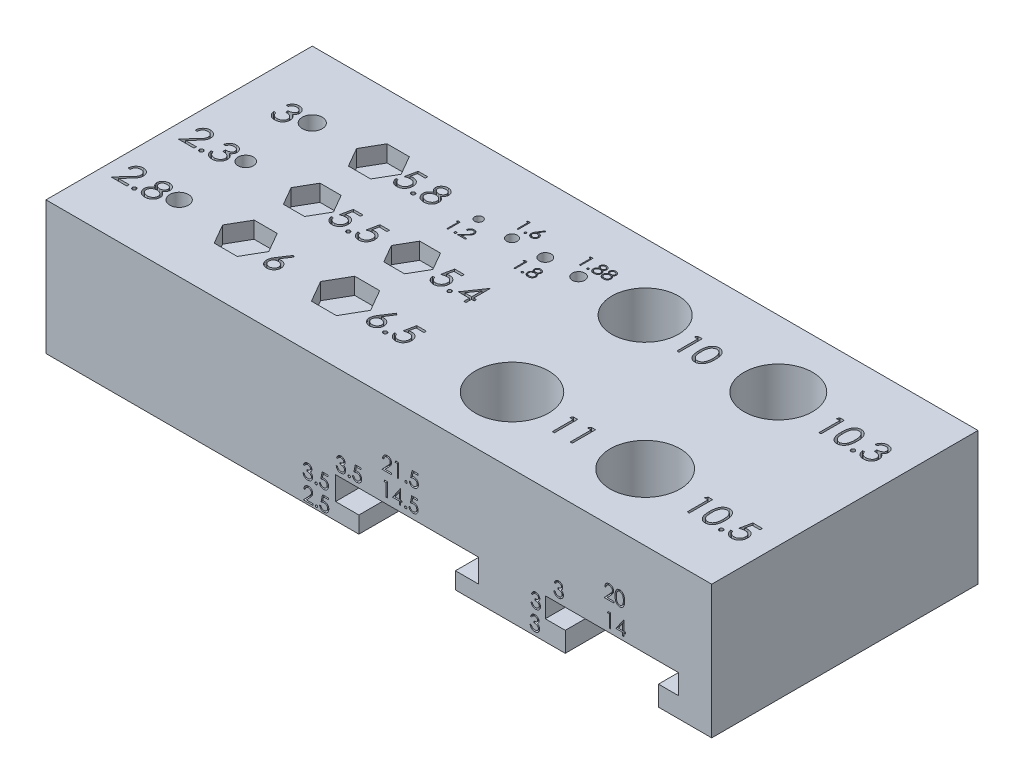
SolidWorks part; units mm, degrees
ref_plane "Front Plane" through (0, 0, 0) normal (0, 0, 1) x (1, 0, 0)
ref_plane "Top Plane" through (0, 0, 0) normal (0, 1, 0) x (1, 0, 0)
ref_plane "Right Plane" through (0, 0, 0) normal (1, 0, 0) x (0, 0, -1)
sketch "Sketch1" plane through (0, 0, 0) normal (0, 1, 0) x (1, 0, 0)
  line L1 (-50, 20) -> (50, 20)
  line L2 (-50, 20) -> (-50, -20)
  line L3 (-50, -20) -> (50, -20)
  line L4 (50, 20) -> (50, -20)
  line L5 (-50, 20) -> (50, -20) construction
  line L6 (-50, -20) -> (50, 20) construction
  point P0 (0, 0)
  dimension "D1" = 100
  dimension "D2" = 40
extrude "Boss-Extrude1" add sketch "Sketch1" along normal blind 15 and the other way blind 5
sketch "Sketch2" plane through (0, 15, 0) normal (0, 1, 0) x (1, 0, 0)
  line L0 (-55.0226, 0) -> (74.4605, 0) construction
  line L1 (0, -20.9292) -> (0, 35.5333) construction
  line L2 (-15, 35.5333) -> (-15, -25.6601) construction
  line L3 (-30, 35.5333) -> (-30, -25.6601) construction
  line L4 (-45, 35.5333) -> (-45, -26.8859) construction
  line L5 (-55.0226, 10) -> (73.221, 10) construction
  line L6 (-26.8246, 0) -> (-28.4123, 2.75)
  line L7 (-28.4123, 2.75) -> (-31.5877, 2.75)
  line L8 (-31.5877, 2.75) -> (-33.1754, 0)
  line L9 (-33.1754, 0) -> (-31.5877, -2.75)
  line L10 (-31.5877, -2.75) -> (-28.4123, -2.75)
  line L11 (-28.4123, -2.75) -> (-26.8246, 0)
  line L12 (-55.0226, -10) -> (70.5333, -10) construction
  line L14 (-26.6514, 10) -> (-28.3257, 12.9)
  line L15 (-28.3257, 12.9) -> (-31.6743, 12.9)
  line L16 (-31.6743, 12.9) -> (-33.3486, 10)
  line L17 (-33.3486, 10) -> (-31.6743, 7.1)
  line L18 (-31.6743, 7.1) -> (-28.3257, 7.1)
  line L19 (-28.3257, 7.1) -> (-26.6514, 10)
  line L20 (-26.5359, -10) -> (-28.2679, -7)
  line L21 (-28.2679, -7) -> (-31.7321, -7)
  line L22 (-31.7321, -7) -> (-33.4641, -10)
  line L23 (-33.4641, -10) -> (-31.7321, -13)
  line L24 (-31.7321, -13) -> (-28.2679, -13)
  line L25 (-28.2679, -13) -> (-26.5359, -10)
  line L26 (-11.2472, -10) -> (-13.1236, -6.75)
  line L27 (-13.1236, -6.75) -> (-16.8764, -6.75)
  line L28 (-16.8764, -6.75) -> (-18.7528, -10)
  line L29 (-18.7528, -10) -> (-16.8764, -13.25)
  line L30 (-16.8764, -13.25) -> (-13.1236, -13.25)
  line L31 (-13.1236, -13.25) -> (-11.2472, -10)
  line L32 (-11.8823, 0) -> (-13.4412, 2.7)
  line L33 (-13.4412, 2.7) -> (-16.5588, 2.7)
  line L34 (-16.5588, 2.7) -> (-18.1177, 0)
  line L35 (-18.1177, 0) -> (-16.5588, -2.7)
  line L36 (-16.5588, -2.7) -> (-13.4412, -2.7)
  line L37 (-13.4412, -2.7) -> (-11.8823, 0)
  circle A0 centre (-30, 0) radius 2.75 construction
  circle A1 centre (-30, 10) radius 2.9 construction
  circle A2 centre (-30, -10) radius 3 construction
  circle A3 centre (-15, -10) radius 3.25 construction
  circle A4 centre (-15, 0) radius 2.7 construction
  point P11 (-30, 0)
  point P24 (-30, 10)
  point P25 (-30, -10)
  point P35 (-15, -10)
  point P43 (-15, 0)
  point P44 (-15, 10)
  point P54 (-32.5981, -11.5)
  point P62 (-27.4019, -8.5)
  point P63 (-32.3816, -1.375)
  point P64 (-45, 10)
  point P65 (-45, 0)
  point P66 (-45, -10)
  dimension "D1" = 15
  dimension "D2" = 15
  dimension "D3" = 15
  dimension "D4" = 6
  dimension "D5" = 10
  dimension "D6" = 10
  dimension "D7" = 5.5
  dimension "D8" = 5.8
  dimension "D9" = 6.5
  dimension "D10" = 5.4
extrude "Cut-Extrude2" cut sketch "Sketch2" against normal blind 2.5
sketch "Sketch4" plane through (0, 15, 0) normal (0, 1, 0) x (1, 0, 0)
  line L0 (-51.3652, 0) -> (12.805, 0) construction
  line L1 (-33.3486, 10) -> (13.2716, 10) construction
  line L2 (-33.4641, -10) -> (12.805, -10) construction
  line L3 (-26.6514, 15.317) -> (-26.6514, -17.9931) construction
  text T0 "5.5\r\n"
  text T1 "5.8\r\n"
  text T2 "6\r\n"
  text T3 "6.5"
  text T4 "5.4"
  point P9 (-26.8246, 0)
  point P10 (-11.8823, 0)
  point P12 (-26.6514, 10)
  point P14 (-26.5359, -10)
  point P16 (-11.2472, -10)
extrude "Cut-Extrude3" cut sketch "Sketch4" against normal blind 1
sketch "Sketch5" plane through (0, 15, 0) normal (0, 1, 0) x (1, 0, 0)
  line L0 (-53.0216, 0) -> (7.0622, 0) construction
  line L1 (-40, 20.4528) -> (-40, -20.8884) construction
  line L2 (-50, 20) -> (-50, -20) construction
  line L3 (-53.3145, 10) -> (-2.602, 10) construction
  line L4 (-53.3145, -10) -> (1.0099, -10) construction
  circle A0 centre (-40, 0) radius 1.15
  circle A1 centre (-40, 10) radius 1.5
  circle A2 centre (-40, -10) radius 1.4
  point P11 (-40, 10)
  point P12 (-40, 0)
  point P13 (-40, -10)
  dimension "D4" = 3
  dimension "D5" = 2.3
  dimension "D6" = 2.8
  dimension "D1" = 10
  dimension "D2" = 10
  dimension "D3" = 10
extrude "Cut-Extrude4" cut sketch "Sketch5" against normal through all
sketch "Sketch6" plane through (0, 15, 0) normal (0, 1, 0) x (1, 0, 0)
  text T0 "3"
  text T1 "2.3\r\n"
  text T2 "2.8\r\n"
extrude "Cut-Extrude5" cut sketch "Sketch6" against normal blind 1
sketch "Sketch7" plane through (0, 15, 0) normal (0, 1, 0) x (1, 0, 0)
  line L0 (-58.108, 0) -> (70.6552, 0) construction
  line L1 (10, 29.8768) -> (10, -34.402) construction
  line L2 (30, 29.8768) -> (30, -36.2532) construction
  line L3 (50, -20) -> (50, 20) construction
  line L4 (63.2503, 10) -> (-10.3874, 10) construction
  line L5 (0, -10) -> (69.4211, -10) construction
  circle A0 centre (10, 10) radius 5
  circle A1 centre (30, 10) radius 5.15
  circle A2 centre (30, -10) radius 5.25
  circle A3 centre (10, -10) radius 5.5
  point P13 (10, 10)
  point P14 (30, 10)
  point P15 (30, -10)
  point P16 (10, -10)
  dimension "D5" = 10
  dimension "D6" = 11
  dimension "D7" = 10.5
  dimension "D8" = 10.3
  dimension "D1" = 20
  dimension "D2" = 20
  dimension "D3" = 10
  dimension "D4" = 10
extrude "Cut-Extrude6" cut sketch "Sketch7" against normal blind 10
sketch "Sketch8" plane through (0, 15, 0) normal (0, 1, 0) x (1, 0, 0)
  text T0 "10\r\n"
  text T1 "11"
  text T2 "10.3\r\n"
  text T3 "10.5"
extrude "Cut-Extrude7" cut sketch "Sketch8" against normal blind 1
sketch "Sketch9" plane through (0, 0, 20) normal (0, 0, 1) x (1, 0, 0)
  line L0 (53.7715, 1) -> (-9.5236, 1) construction
  line L1 (45, 17.6721) -> (45, -16.7465) construction
  line L2 (25, 18.1388) -> (25, -16.7465) construction
  line L3 (53.7715, -2) -> (-2.4066, -2) construction
  line L4 (-50, -5) -> (50, -5) construction
  line L5 (50, -5) -> (50, 15) construction
  line L6 (28, -9.1919) -> (28, 15.8625) construction
  line L7 (42, 15.8625) -> (42, -9.1919) construction
  line L8 (-3, -5) -> (-3, -2.5)
  line L9 (28, -5) -> (28, -2)
  line L10 (28, -2) -> (25, -2)
  line L11 (25, -2) -> (25, 1)
  line L12 (25, 1) -> (45, 1)
  line L13 (45, 1) -> (45, -2)
  line L14 (45, -2) -> (42, -2)
  line L15 (42, -2) -> (42, -5)
  line L16 (42, -5) -> (28, -5)
  line L17 (15, -5) -> (15, 11.272) construction
  line L18 (-6.5, -5) -> (-6.5, 13.9547) construction
  line L19 (-3, 16.4059) -> (-3, -11.3441) construction
  line L20 (11.5, 16.8381) -> (11.5, -11.3441) construction
  line L21 (-10.0811, -2.5) -> (47.089, -2.5) construction
  line L22 (-3, -2.5) -> (-6.5, -2.5)
  line L23 (-6.5, -2.5) -> (-6.5, 1)
  line L24 (-6.5, 1) -> (15, 1)
  line L25 (15, 1) -> (15, -2.5)
  line L26 (15, -2.5) -> (11.5, -2.5)
  line L27 (11.5, -2.5) -> (11.5, -5)
  line L28 (11.5, -5) -> (-3, -5)
  point P33 (15, 3.136)
  dimension "D1" = 3
  dimension "D2" = 3
  dimension "D3" = 5
  dimension "D4" = 20
  dimension "D5" = 3
  dimension "D6" = 3
  dimension "D7" = 3.5
  dimension "D8" = 21.5
  dimension "D9" = 2.5
  dimension "D10" = 3.5
  dimension "D11" = 10
extrude "Cut-Extrude9" cut sketch "Sketch9" against normal through all
sketch "Sketch10" plane through (0, 0, 20) normal (0, 0, 1) x (1, 0, 0)
  text T0 "21.5" font "Century Gothic" height in points 8
  text T1 "2.5\r\n" font "Century Gothic" height in points 8
  text T2 "3.5\r\n" font "Century Gothic" height in points 8
  text T3 "3.5" font "Century Gothic" height in points 8
  text T4 "14.5" font "Century Gothic" height in points 8
  text T5 "20" font "Century Gothic" height in points 8
  text T6 "3" font "Century Gothic" height in points 8
  text T7 "14\r\n" font "Century Gothic" height in points 8
  text T8 "3" font "Century Gothic" height in points 8
  text T9 "3" font "Century Gothic" height in points 8
extrude "Cut-Extrude10" cut sketch "Sketch10" against normal blind 1
sketch "Sketch11" plane through (0, 15, 0) normal (0, 1, 0) x (1, 0, 0)
  line L0 (-56.7311, 10) -> (62.4969, 10) construction
  line L1 (50, 20) -> (-50, 20) construction
  line L2 (0, 25.9873) -> (0, -22.5571) construction
  line L3 (-5, 25.9873) -> (-5, -26.7124) construction
  line L4 (-10, 25.9873) -> (-10, -27.416) construction
  line L5 (-15, 29.9774) -> (-15, -29.4263) construction
  circle A0 centre (-15, 10) radius 0.6
  circle A1 centre (-10, 10) radius 0.8
  circle A2 centre (-5, 10) radius 0.9
  circle A3 centre (0, 10) radius 0.94
  dimension "D5" = 1.88
  dimension "D6" = 1.8
  dimension "D7" = 1.6
  dimension "D8" = 1.2
  dimension "D1" = 10
  dimension "D2" = 5
  dimension "D3" = 5
  dimension "D4" = 5
extrude "Cut-Extrude11" cut sketch "Sketch11" against normal through all
sketch "Sketch12" plane through (0, 15, 0) normal (0, 1, 0) x (1, 0, 0)
  text T0 "1.88" font "Century Gothic" height in points 7
  text T1 "1.8" font "Century Gothic" height in points 7
  text T2 "1.6" font "Century Gothic" height in points 7
  text T3 "1.2" font "Century Gothic" height in points 7
extrude "Cut-Extrude12" cut sketch "Sketch12" against normal blind 1
